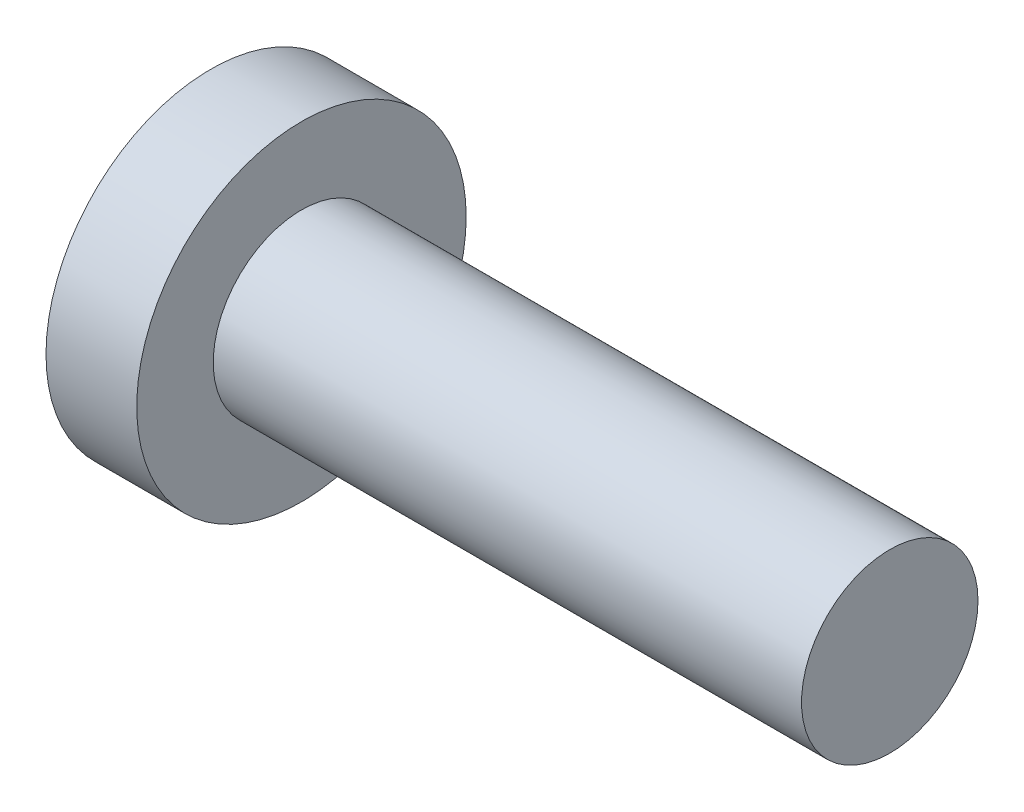
SolidWorks part; units mm, degrees
material "Q235-A"
ref_plane "Front" through (0, 0, 0) normal (0, 0, 1) x (1, 0, 0)
ref_plane "Top" through (0, 0, 0) normal (0, 1, 0) x (1, 0, 0)
ref_plane "Right" through (0, 0, 0) normal (1, 0, 0) x (0, 0, -1)
sketch "Sketch1" plane through (0, 0, 0) normal (0, 0, 1) x (1, 0, 0)
  line L0 (12.4, 1.5) -> (3.4, 1.5)
  line L1 (2.4, 1.8) -> (2.4, 2.8)
  line L2 (2.4, 2.8) -> (0.8575, 2.8)
  line L3 (3.4, 1.5) -> (2.7, 1.5) construction
  line L4 (12.4, 1.5) -> (12.4, 0)
  line L5 (4.5158, 0) -> (-13.5157, 0) construction
  line L6 (12.4, 0) -> (0, 0)
  line L7 (3.4, 1.5) -> (2.4, 1.5)
  line L8 (2.4, 1.5) -> (2.4, 1.8)
  arc A0 (0.8575, 2.8) -> (0, 0) centre (5, 0) ccw
  arc A1 (2.4, 1.8) -> (2.7, 1.5) centre (2.7, 1.8) ccw construction
  dimension "k" = 2.4
revolve "Base" add sketch "Sketch1" angle 360 about L5
cosmetic thread "ThreadCosmetic1" [suppressed] parameters "bb"=8, "THD_MINOR"=2.459
sketch "Sketch6" plane through (0, 0, 0) normal (1, 0, 0) x (0, 0, -1)
  line L0 (-1.9271, 0) -> (2.0512, 0) construction
  line L1 (0, 1.8651) -> (0, -2.0207) construction
  line L2 (0.3, 0.3) -> (0.3, 1.5)
  line L3 (0.3, 1.5) -> (-0.3, 1.5)
  line L4 (-0.3, 0.3) -> (-0.3, 1.5)
  line L5 (0.3, 0.3) -> (1.5, 0.3)
  line L6 (1.5, 0.3) -> (1.5, -0.3)
  line L7 (-1.5, 0.3) -> (-1.5, -0.3)
  line L8 (-0.3, 0.3) -> (-1.5, 0.3)
  line L9 (-0.3, -0.3) -> (-1.5, -0.3)
  line L10 (0.3, -0.3) -> (1.5, -0.3)
  line L11 (-0.3, -0.3) -> (-0.3, -1.5)
  line L12 (0.3, -1.5) -> (-0.3, -1.5)
  line L13 (0.3, -0.3) -> (0.3, -1.5)
  point P16 (-1.5, 0)
  point P17 (1.5, 0)
extrude "CrossRecess" cut sketch "Sketch6" along normal blind 1.68
fillet "Fillet5" radius 0.3 4 edges at (0.849, -0.3, 0.3) (0.849, -0.3, -0.3) (0.849, 0.3, 0.3) (0.849, 0.3, -0.3)
draft "Draft1" type of draft neutral plane draft angle 30 neutral plane "Right" faces to draft 4 face at (0.9575, -1.5, 0) face at (0.9575, 0, -1.5) face at (0.9575, 0, 1.5) face at (0.9575, 1.5, 0) neutral plane through (0, 0, 0) neutral plane normal (1, 0, 0) reverse direction yes parameters "D1"=30
sketch "Sketch7" plane through (0, 0, 0) normal (1, 0, 0) x (0, 0, -1)
  line L0 (-2.0126, 0) -> (1.9757, 0) construction
  line L1 (0, 1.9314) -> (0, -2.0126) construction
  line L2 (0, 0) -> (1.5555, 1.5555) construction
  line L3 (0, 0.4483) -> (1.0607, 1.0607)
  line L4 (-1.5402, 1.5402) -> (0, 0) construction
  line L5 (0.4483, 0) -> (1.0607, 1.0607)
  line L6 (0, -0.4483) -> (1.0607, -1.0607)
  line L7 (0.4483, 0) -> (1.0607, -1.0607)
  line L8 (-0.4483, 0) -> (-1.0607, -1.0607)
  line L9 (0, -0.4483) -> (-1.0607, -1.0607)
  line L10 (-0.4483, 0) -> (-1.0607, 1.0607)
  line L11 (0, 0.4483) -> (-1.0607, 1.0607)
  dimension "D3" = 15
extrude "Cut-Extrude3" [suppressed] cut sketch "Sketch7" along normal blind 40.2 draft 9
sketch "Sketch8" plane through (0, 0, 0) normal (0, 0, 1) x (1, 0, 0)
  line L0 (-12.6, 1.5) -> (-13.85, 1.2295)
  line L1 (-13.85, 1.2295) -> (2.4, 1.2295)
  line L2 (12.4, -1.5) -> (12.4, 1.5) construction
  line L3 (2.4, -2.8) -> (2.4, 2.8) construction
  line L6 (2.4, 1.2295) -> (2.4, 2.8)
  line L7 (2.4, 2.8) -> (-12.6, 2.8)
  line L8 (-12.6, 2.8) -> (-12.6, 1.5)
  line L9 (73.4853, 0) -> (63.9694, 0) construction
  dimension "x" = 1.25
sketch "Sketch9" plane through (0, 0, 0) normal (0, 0, 1) x (1, 0, 0)
  line L0 (12.4, 1.2657) -> (12.5352, 1.5)
  line L1 (12.5352, 1.5) -> (12.5352, 1.7705)
  line L2 (12.5352, 1.7705) -> (12.2647, 1.7705)
  line L3 (12.2647, 1.7705) -> (12.2647, 1.5)
  line L4 (12.2647, 1.5) -> (12.4, 1.2657)
  line L5 (12.4, -1.5) -> (12.4, 1.5) construction
  line L6 (0, 0) -> (76.7811, 0) construction
  dimension "D2" = 0.2705
revolve "Cut-Revolve10" [suppressed] cut sketch "Sketch9" angle 360 about L6
pattern_linear "LPattern10" [suppressed] count 25 spacing 0.3246 along (-1, 0, 0) of bodies 105
equation "\"D1@Sketch6\" = \"m@Sketch6\" / 5"
equation "\"D1@CrossRecess\" = 0.7*\"k@Sketch1\""
equation "\"D1@Sketch9\" = \"d@Sketch1\" "
equation "\"D2@Sketch9\" =  ( \"d@Sketch1\" - \"THD_MINOR@ThreadCosmetic1\" )  / 2"
equation "\"D3@LPattern10\" =\"D2@Sketch9\" * 1.2"
equation "\"D1@LPattern10\" = \"bb@ThreadCosmetic1\" / \"D3@LPattern10\" "
